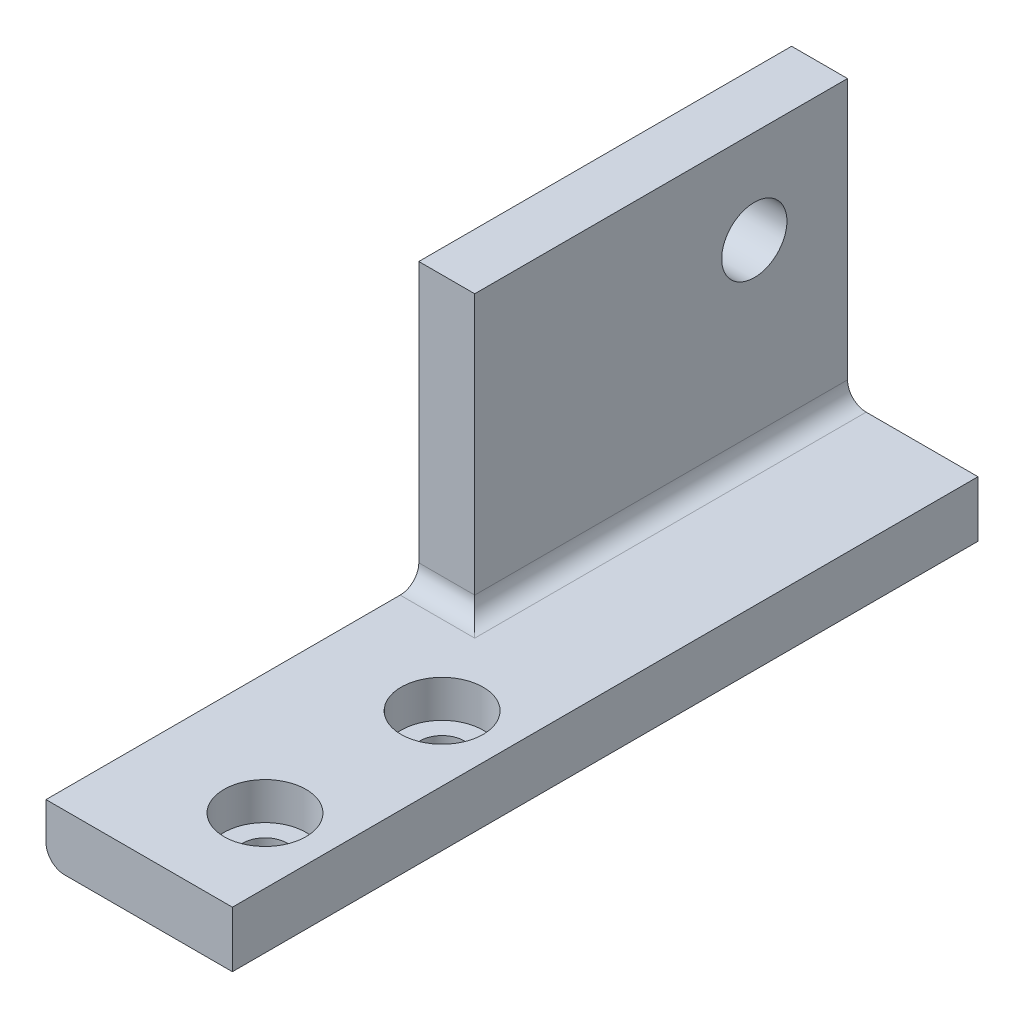
SolidWorks part; units mm, degrees
ref_plane "Front Plane" through (0, 0, 0) normal (0, 0, 1) x (1, 0, 0)
ref_plane "Top Plane" through (0, 0, 0) normal (0, 1, 0) x (1, 0, 0)
ref_plane "Right Plane" through (0, 0, 0) normal (1, 0, 0) x (0, 0, -1)
sketch "Sketch1" plane through (0, 0, 0) normal (0, 1, 0) x (1, 0, 0)
  line L0 (6.5, 5.25) -> (6.5, 14.75) construction
  line L1 (0, 0) -> (10, 0)
  line L2 (0, 0) -> (0, 20)
  line L3 (0, 20) -> (10, 20)
  line L4 (10, 0) -> (10, 20)
  circle A0 centre (6.5, 5.25) radius 1.175
  circle A1 centre (6.5, 14.75) radius 1.175
  point P9 (6.5, 10)
  point P10 (10, 10)
  dimension "D3" = 9.5
  dimension "D4" = 2.35
  dimension "D5" = 2.35
  dimension "D6" = 6.5
  dimension "D1" = 20
  dimension "D2" = 10
extrude "Boss-Extrude1" add sketch "Sketch1" along normal blind 3
sketch "Sketch2" plane through (0, 3, 0) normal (0, 1, 0) x (1, 0, 0)
  point P0 (6.5, 14.75)
  point P1 (6.5, 5.25)
hole_wizard "CBORE for M2 SHCS1" positions "Sketch2" profile "Sketch3" counterbore size "M2" standard "ANSI Metric" end condition through all
sketch "Sketch3" plane through (6.5, 3, -14.75) normal (1, 0, 0) x (0, 0, 1)
  line L0 (0, 0) -> (0, 3)
  line L1 (0, 3) -> (1.2, 3)
  line L3 (1.2, 3) -> (1.2, 2)
  line L4 (1.2, 2) -> (2.2, 2)
  line L5 (2.2, 2) -> (2.2, 0)
  line L7 (2.2, 0) -> (0, 0)
  line L11 (0, -6.35) -> (0, 107.95) construction
  dimension "Thru Hole Dia." = 2.4
  dimension "Thru Hole Depth" = 3
  dimension "C'Bore Dia." = 4.4
  dimension "C'Bore Depth" = 2
sketch "Sketch6" plane through (0, 0, -20) normal (0, 0, -1) x (-1, 0, 0)
  line L1 (0, 0) -> (-10, 0)
  line L2 (0, 0) -> (0, 3)
  line L3 (0, 3) -> (-10, 3)
  line L4 (-10, 0) -> (-10, 3)
  line L5 (-10, 3) -> (0, 3) construction
  line L6 (-10, 3) -> (-10, 0) construction
  dimension "D1" = 0
extrude "Boss-Extrude2" add sketch "Sketch6" along normal blind 20
sketch "Sketch8" plane through (0, 3, 0) normal (0, 1, 0) x (1, 0, 0)
  line L2 (0, 40) -> (3, 40)
  line L3 (0, 40) -> (0, 20)
  line L4 (0, 20) -> (3, 20)
  line L5 (3, 40) -> (3, 20)
  dimension "D1" = 3
  dimension "D2" = 20
extrude "Boss-Extrude3" add sketch "Sketch8" along normal blind 15
sketch "Sketch9" plane through (3, 0, 0) normal (1, 0, 0) x (0, 0, -1)
  line L1 (0, 3) -> (40, 3) construction
  line L2 (40, 18) -> (40, 3) construction
  circle A0 centre (35, 13) radius 1.75
  dimension "D1" = 10
  dimension "D2" = 5
  dimension "D3" = 3.5
extrude "Cut-Extrude1" cut sketch "Sketch9" against normal through all
fillet "Fillet1" radius 1 2 edges at (1.5, 3, -20) (3, 3, -30)
fillet "Fillet2" radius 1 1 edges at (0, 0, -20)
